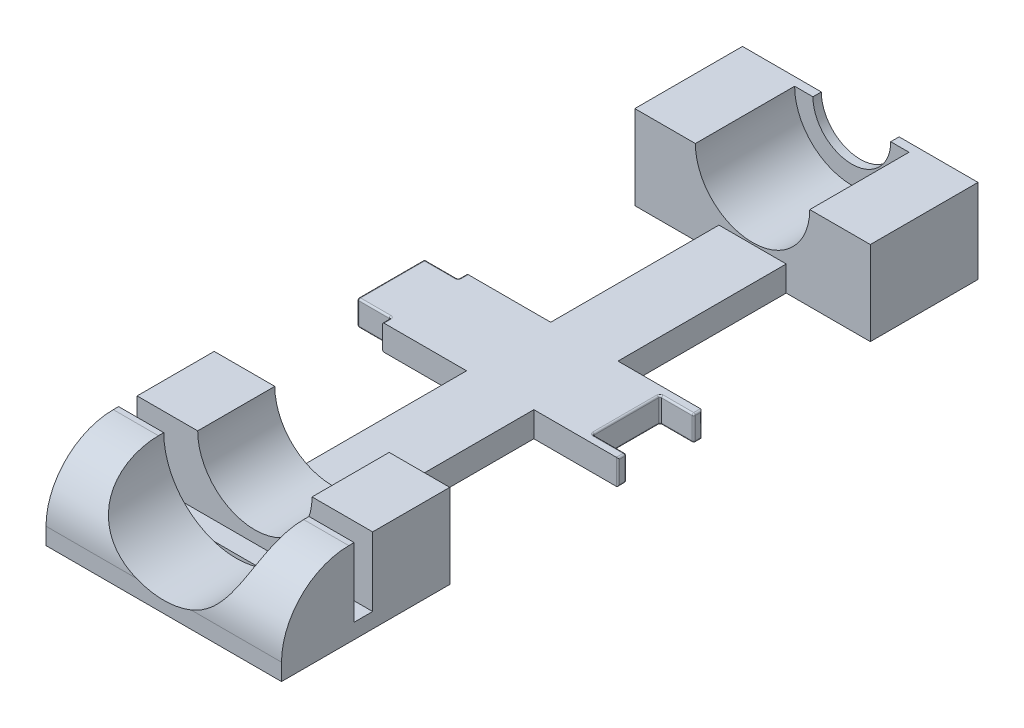
SolidWorks part; units mm, degrees
ref_plane "Front Plane" through (0, 0, 0) normal (0, 0, 1) x (1, 0, 0)
ref_plane "Top Plane" through (0, 0, 0) normal (0, 1, 0) x (1, 0, 0)
ref_plane "Right Plane" through (0, 0, 0) normal (1, 0, 0) x (0, 0, -1)
sketch "Sketch1" plane through (0, 0, 0) normal (0, 1, 0) x (1, 0, 0)
  line L1 (-14, -45) -> (14, -45)
  line L2 (-14, -45) -> (-14, 45)
  line L3 (-14, 45) -> (14, 45)
  line L4 (14, -45) -> (14, 45)
  line L5 (-14, -45) -> (14, 45) construction
  line L6 (-14, 45) -> (14, -45) construction
  point P0 (0, 0)
  dimension "D1" = 90
  dimension "D2" = 28
extrude "Boss-Extrude1" add sketch "Sketch1" along normal blind 10
sketch "Sketch3" plane through (0, 10, 0) normal (0, 1, 0) x (1, 0, 0)
  line L0 (0, 45) -> (0, -45) construction
  line L1 (14, 45) -> (-14, 45) construction
  line L2 (-14, -45) -> (14, -45) construction
  line L4 (0, 45) -> (-4.625, 45)
  line L5 (0, 45) -> (0, 34.8)
  line L6 (0, 34.8) -> (-4.625, 34.8)
  line L7 (-4.625, 45) -> (-4.625, 34.8)
  line L8 (0, 45) -> (-4.625, 34.8) construction
  line L9 (0, 34.8) -> (-4.625, 45) construction
  point P9 (-2.3125, 39.9)
  dimension "D2" = 4.625
sketch "Sketch4" plane through (0, 10, 0) normal (0, 1, 0) x (1, 0, 0)
  line L0 (0, 36.8) -> (0, -45) construction
  line L2 (-14, -45) -> (14, -45) construction
  line L4 (0, 36.8) -> (-6.8, 36.8)
  line L5 (0, 36.8) -> (0, -34.2)
  line L6 (0, -34.2) -> (-6.8, -34.2)
  line L7 (-6.8, 36.8) -> (-6.8, -34.2)
  line L8 (0, 36.8) -> (-6.8, -34.2) construction
  line L9 (0, -34.2) -> (-6.8, 36.8) construction
  point P9 (-3.4, 1.3)
  dimension "D1" = 71
  dimension "D2" = 6.8
revolve "Syringe Body slot" cut sketch "Sketch4" angle 360 about L5
sketch "Sketch5" plane through (0, 10, 0) normal (0, 1, 0) x (1, 0, 0)
  line L0 (-13.75, -35.2671) -> (13.75, -35.2671) construction
  line L1 (6.8, -34.2) -> (-6.8, -34.2) construction
  line L2 (-14, 45) -> (-14, -45) construction
  line L3 (0, -34.2) -> (0, -35.2671) construction
  line L4 (14, -45) -> (14, 45) construction
  line L5 (-14, -36.3671) -> (14, -36.3671)
  line L6 (-14, -36.3671) -> (-14, -34.1671)
  line L7 (-14, -34.1671) -> (14, -34.1671)
  line L8 (14, -36.3671) -> (14, -34.1671)
  line L9 (-14, -36.3671) -> (14, -34.1671) construction
  line L10 (-14, -34.1671) -> (14, -36.3671) construction
  point P6 (0, -35.2671)
  dimension "D2" = 13.75
extrude "Flange Slot" cut sketch "Sketch5" against normal blind 8.2
sketch "Sketch6" plane through (0, 10, 0) normal (0, 1, 0) x (1, 0, 0)
  line L0 (0, -36.3671) -> (0, -45) construction
  line L1 (-14, -36.3671) -> (14, -36.3671) construction
  line L2 (-14, -45) -> (14, -45) construction
  line L4 (0, -45) -> (-8.6329, -45)
  line L5 (0, -45) -> (0, -36.3671)
  line L6 (0, -36.3671) -> (-8.6329, -36.3671)
  line L7 (-8.6329, -45) -> (-8.6329, -36.3671)
  line L8 (0, -45) -> (-8.6329, -36.3671) construction
  line L9 (0, -36.3671) -> (-8.6329, -45) construction
  point P9 (-4.3165, -40.6835)
revolve "Plunger Slot" cut sketch "Sketch6" angle 360 about L5
revolve "Barrell Slot" cut sketch "Sketch3" angle 360 about L5
sketch "Sketch17" plane through (0, 10, 0) normal (0, 1, 0) x (1, 0, 0)
  line L0 (-9.65, -34.2) -> (-9.65, 37.8) construction
  line L2 (4.625, 45) -> (-4.625, 45) construction
  line L3 (-19.0449, 52.2) -> (19.0449, 52.2)
  line L4 (-19.0449, 52.2) -> (-19.0449, 37.8)
  line L5 (-19.0449, 37.8) -> (19.0449, 37.8)
  line L6 (19.0449, 52.2) -> (19.0449, 37.8)
  line L7 (-19.0449, 52.2) -> (19.0449, 37.8) construction
  line L8 (-19.0449, 37.8) -> (19.0449, 52.2) construction
  point P4 (0, 45)
  dimension "D1" = 72
extrude "Cut-Extrude4" cut sketch "Sketch17" against normal through all both and the other way through all
sketch "Sketch18" plane through (0, 10, 0) normal (0, 1, 0) x (1, 0, 0)
  line L1 (-14, -25) -> (14, -25)
  line L2 (-14, -25) -> (-14, 25)
  line L3 (-14, 25) -> (14, 25)
  line L4 (14, -25) -> (14, 25)
  line L5 (-14, -25) -> (14, 25) construction
  line L6 (-14, 25) -> (14, -25) construction
  point P0 (0, 0)
  dimension "D1" = 50
  dimension "D2" = 28
extrude "Syringe Bay" cut sketch "Sketch18" against normal blind 7
fillet "Syringe plunger left" radius 8 1 edges at (11.3165, 10, 45)
fillet "Syringe plunger right" radius 8 1 edges at (-11.3165, 10, 45)
sketch "Sketch19" plane through (0, 3, 0) normal (0, 1, 0) x (1, 0, 0)
  line L0 (0, 25) -> (0, -25) construction
  line L1 (-14, 25) -> (-4, 25)
  line L2 (-14, 25) -> (-14, 5)
  line L3 (-14, 5) -> (-4, 5)
  line L4 (-4, 25) -> (-4, 5)
  line L5 (-6.8, 25) -> (6.8, 25) construction
  line L6 (-14, -25) -> (14, -25) construction
  line L7 (-14, 0) -> (14, 0) construction
  line L8 (-14, 25) -> (-14, -25) construction
  line L9 (14, -25) -> (14, 25) construction
  line L10 (-14, -5) -> (-4, -5)
  line L11 (-4, -25) -> (-4, -5)
  line L12 (-14, -25) -> (-4, -25)
  line L13 (-14, -25) -> (-14, -5)
  line L14 (14, -25) -> (14, -5)
  line L15 (14, -25) -> (4, -25)
  line L16 (4, -25) -> (4, -5)
  line L17 (14, -5) -> (4, -5)
  line L18 (14, 5) -> (4, 5)
  line L19 (4, 25) -> (4, 5)
  line L20 (14, 25) -> (4, 25)
  line L21 (14, 25) -> (14, 5)
  dimension "D1" = 20
  dimension "D2" = 10
extrude "Cut-Extrude5" cut sketch "Sketch19" against normal blind 10
sketch "Sketch24" plane through (-14, 0, 0) normal (-1, 0, 0) x (0, 0, 1)
  line L0 (0, 3) -> (0, 0) construction
  line L1 (-5, 3) -> (5, 3) construction
  line L2 (-5, 1.5) -> (5, 1.5) construction
  line L3 (-5, 0) -> (-5, 3) construction
  line L4 (5, 0) -> (5, 3) construction
  line L6 (-4, 0) -> (4, 0)
  line L7 (-4, 0) -> (-4, 3)
  line L8 (-4, 3) -> (4, 3)
  line L9 (4, 0) -> (4, 3)
  line L10 (-4, 0) -> (4, 3) construction
  line L11 (-4, 3) -> (4, 0) construction
  point P11 (0, 1.5)
  dimension "D1" = 3
  dimension "D2" = 8
extrude "Boss-Extrude3" add sketch "Sketch24" along normal blind 4
sketch "Sketch25" plane through (14, 0, 0) normal (1, 0, 0) x (0, 0, -1)
  line L0 (0, 3) -> (0, 0) construction
  line L1 (-5, 3) -> (5, 3) construction
  line L3 (-4, 0) -> (4, 0)
  line L4 (-4, 0) -> (-4, 3)
  line L5 (-4, 3) -> (4, 3)
  line L6 (4, 0) -> (4, 3)
  line L7 (-4, 0) -> (4, 3) construction
  line L8 (-4, 3) -> (4, 0) construction
  point P5 (0, 1.5)
  dimension "D1" = 3
  dimension "D2" = 8
extrude "Cut-Extrude6" cut sketch "Sketch25" against normal blind 4
fillet "Fillet1" radius 0.2 16 edges at (10, 0, 0) (10, 3, 0) (14, 0, 4.5) (14, 1.5, 5) (14, 3, 4.5) (12, 0, 4) (12, 3, 4) (10, 1.5, 4) (14, 1.5, 4) (14, 0, -4.5) (14, 3, -4.5) (14, 1.5, -5) (12, 0, -4) (10, 1.5, -4) (12, 3, -4) (14, 1.5, -4)
fillet "Fillet2" radius 0.2 14 edges at (-14, 0, 4.5) (-14, 3, 4.5) (-14, 3, -4.5) (-14, 0, -4.5) (-16, 0, 4) (-16, 3, 4) (-14, 1.5, 4) (-18, 0, 0) (-18, 3, 0) (-18, 1.5, 4) (-16, 3, -4) (-18, 1.5, -4) (-16, 0, -4) (-14, 1.5, -4)
